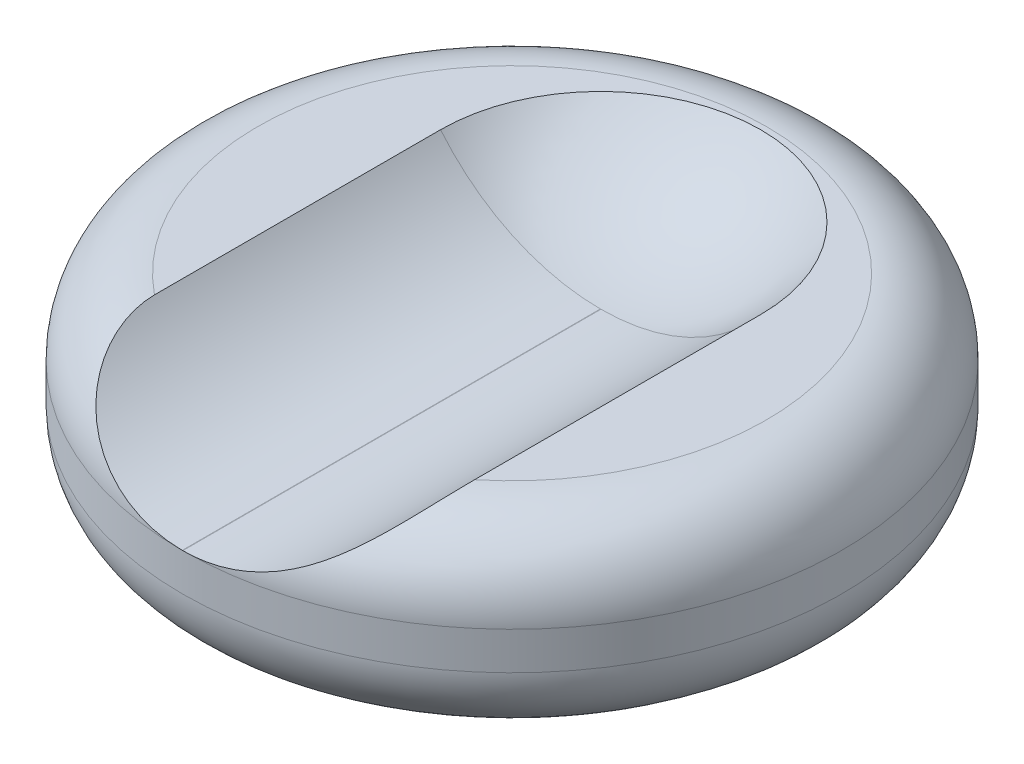
SolidWorks part; units mm, degrees
ref_plane "Front Plane" through (0, 0, 0) normal (0, 0, 1) x (1, 0, 0)
ref_plane "Top Plane" through (0, 0, 0) normal (0, 1, 0) x (1, 0, 0)
ref_plane "Right Plane" through (0, 0, 0) normal (1, 0, 0) x (0, 0, -1)
sketch "Sketch1" plane through (0, 0, 0) normal (0, 1, 0) x (1, 0, 0)
  circle A0 centre (0, 0) radius 17.5
  dimension "D1" = 35
extrude "Boss-Extrude1" add sketch "Sketch1" along normal blind 10
fillet "Fillet1" radius 4 2 edges at (0, 0, 17.5) (0, 10, 17.5)
sketch "Sketch2" plane through (0, 10, 0) normal (0, 1, 0) x (1, 0, 0)
  line L0 (-8.5, -15.2971) -> (-8.5, 4.7029)
  line L1 (8.5, -15.2971) -> (8.5, 4.7029)
  circle A0 centre (0, 0) radius 17.5 construction
  arc A1 (-8.5, 4.7029) -> (8.5, 4.7029) centre (0, 4.7029) cw
  arc A2 (-8.5, -15.2971) -> (8.5, -15.2971) centre (0, -15.2971) ccw
  dimension "D1" = 20
  dimension "D2" = 17
extrude "Cut-Extrude1" cut sketch "Sketch2" against normal blind 4
fillet "Fillet2" radius 11 2 edges at (8.5, 6, 5.2971) (-8.5, 6, 5.2971)
